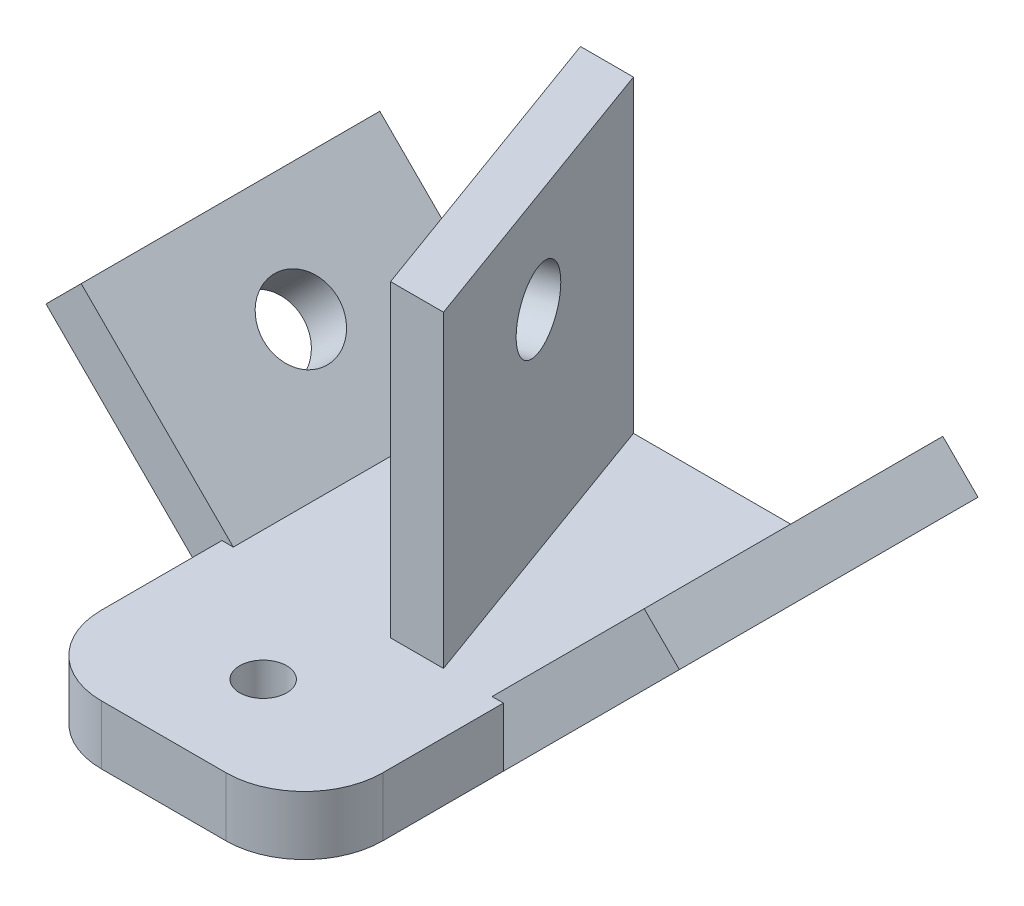
SolidWorks part; units mm, degrees
ref_plane "Front Plane" through (0, 0, 0) normal (0, 0, 1) x (1, 0, 0)
ref_plane "Top Plane" through (0, 0, 0) normal (0, 1, 0) x (1, 0, 0)
ref_plane "Right Plane" through (0, 0, 0) normal (1, 0, 0) x (0, 0, -1)
sketch "Sketch1" plane through (0, 0, 0) normal (0, 0, 1) x (1, 0, 0)
  line L0 (-35.921, 35.921) -> (0, 0)
  line L1 (0, 0) -> (35.921, 35.921)
  line L2 (35.921, 35.921) -> (40.4112, 31.4309)
  line L3 (40.4112, 31.4309) -> (0, -8.9803)
  line L4 (0, -8.9803) -> (-40.4112, 31.4309)
  line L5 (-40.4112, 31.4309) -> (-35.921, 35.921)
  line L6 (0, -8.9803) -> (0, 0) construction
  dimension "D1" = 6.35
  dimension "D2" = 50.8
extrude "Boss-Extrude1" add sketch "Sketch1" along normal mid plane 38.1
sketch "Sketch2" plane through (0, 0, 0) normal (0, 1, 0) x (1, 0, 0)
  line L0 (-10.3124, 19.05) -> (-3.5549, 19.05)
  line L1 (0, 19.05) -> (-35.921, 19.05) construction
  line L2 (-3.5549, 19.05) -> (10.3124, -19.05)
  line L3 (35.921, -19.05) -> (0, -19.05) construction
  line L4 (10.3124, -19.05) -> (3.5549, -19.05)
  line L5 (3.5549, -19.05) -> (-10.3124, 19.05)
  line L6 (-6.9336, 19.05) -> (6.9336, -19.05) construction
  line L7 (0, -19.05) -> (-35.921, -19.05) construction
  point P10 (0, 0)
  dimension "D1" = 6.35
  dimension "D2" = 70
extrude "Boss-Extrude2" add sketch "Sketch2" against normal up to body and the other way blind 50.8 from offset 5.08 separate body
sketch "Sketch3" plane through (-4.4901, -4.4901, 0) normal (-0.7071, -0.7071, 0) x (0, 0, 1)
  line L0 (19.05, 50.8) -> (-19.05, 50.8) construction
  circle A0 centre (0, 38.1) radius 4.7625
  point P4 (0, 50.8)
  dimension "D1" = 9.525
  dimension "D2" = 12.7
extrude "Cut-Extrude1" cut sketch "Sketch3" against normal up to next
mirror "Mirror1" about plane through (0, 0, 0) normal (1, 0, 0) of "Cut-Extrude1"
sketch "Sketch4" plane through (2.9835, 0, -1.0859) normal (0.9397, 0, -0.342) x (-0.342, 0, -0.9397)
  line L0 (-21.4282, 55.88) -> (19.117, 55.88) construction
  circle A0 centre (-1.1556, 43.18) radius 4.7625
  point P4 (-1.1556, 55.88)
  dimension "D2" = 9.525
  dimension "D1" = 12.7
extrude "Cut-Extrude2" cut sketch "Sketch4" against normal up to next
sketch "Sketch5" plane through (0, 0, 19.05) normal (0, 0, 1) x (1, 0, 0)
  line L0 (-16.51, 16.51) -> (16.51, 16.51)
  line L1 (0, 0) -> (-35.921, 35.921) construction
  line L2 (35.921, 35.921) -> (10.3124, 10.3124) construction
  line L3 (16.51, 16.51) -> (0, 0)
  line L4 (0, 0) -> (-16.51, 16.51)
  dimension "D1" = 16.51
extrude "Boss-Extrude3" add sketch "Sketch5" against normal up to surface (38.1 mm away) up to face at (-2.7735, 25.1351, -19.05)
chamfer "Chamfer1" distance 25.4 angle 45 1 edges at (0, -8.9803, 0)
sketch "Sketch6" plane through (0, 8.9803, 0) normal (0, -1, 0) x (1, 0, 0)
  line L1 (-17.9605, 19.05) -> (17.9605, 19.05)
  line L2 (-17.9605, 19.05) -> (-17.9605, 44.45)
  line L3 (-17.9605, 44.45) -> (17.9605, 44.45)
  line L4 (17.9605, 19.05) -> (17.9605, 44.45)
  line L5 (-17.9605, 19.05) -> (17.9605, 44.45) construction
  line L6 (-17.9605, 44.45) -> (17.9605, 19.05) construction
  point P4 (0, 31.75)
  dimension "D1" = 25.4
extrude "Boss-Extrude4" add sketch "Sketch6" against normal up to surface (7.5297 mm away) up to face at (-9.9444, 16.51, 0)
sketch "Sketch7" plane through (0, 16.51, 0) normal (0, 1, 0) x (1, 0, 0)
  line L0 (-17.9605, -44.45) -> (-17.9605, -19.05) construction
  line L1 (17.9605, -44.45) -> (-17.9605, -44.45) construction
  circle A0 centre (0, -31.75) radius 3
  point P4 (-17.9605, -31.75)
  point P7 (0, -44.45)
  dimension "D1" = 6
extrude "Cut-Extrude3" cut sketch "Sketch7" against normal through all
fillet "Fillet1" radius 10 2 edges at (17.9605, 12.7451, 44.45) (-17.9605, 12.7451, 44.45)
